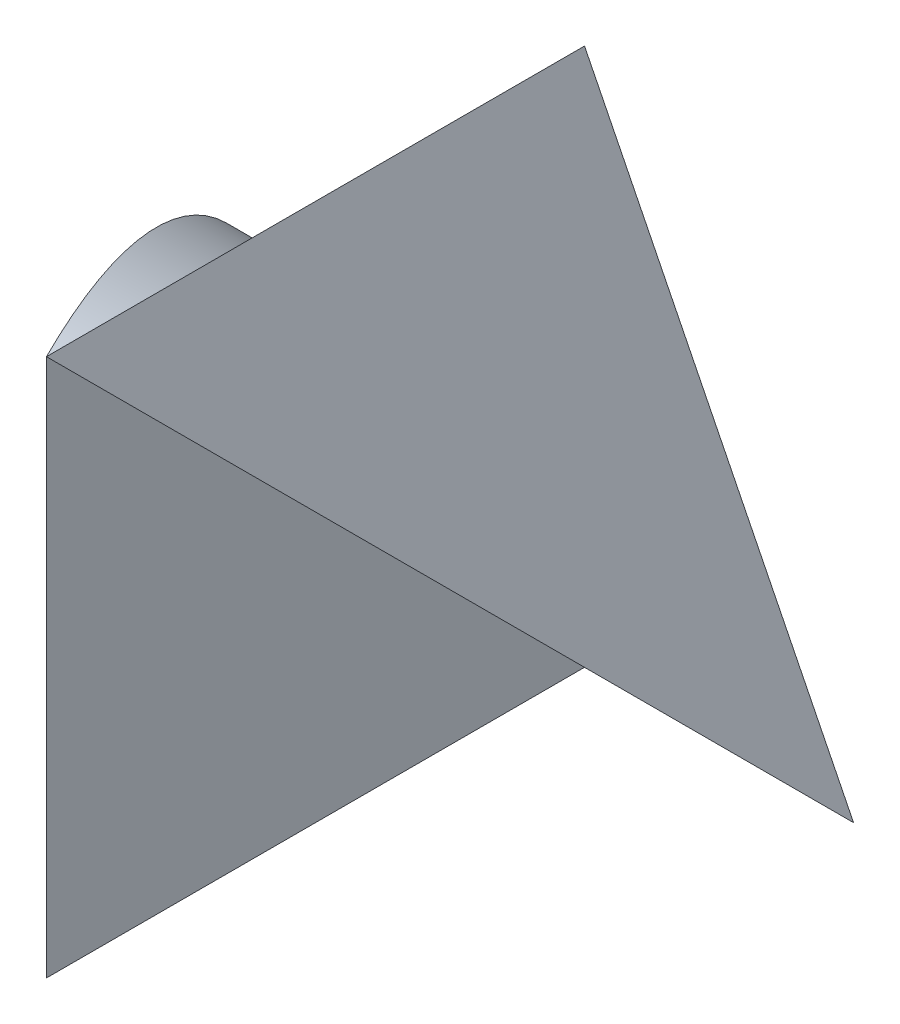
SolidWorks part; units mm, degrees
ref_plane "Front" through (0, 0, 0) normal (0, 0, 1) x (1, 0, 0)
ref_plane "Top" through (0, 0, 0) normal (0, 1, 0) x (1, 0, 0)
ref_plane "Right" through (0, 0, 0) normal (1, 0, 0) x (0, 0, -1)
sketch "Sketch1" plane through (0, 0, 0) normal (0, 1, 0) x (1, 0, 0)
  line L1 (-2, -2) -> (2, -2)
  line L2 (-2, -2) -> (-2, 2)
  line L3 (-2, 2) -> (2, 2)
  line L4 (2, -2) -> (2, 2)
  line L5 (-2, -2) -> (2, 2) construction
  line L6 (-2, 2) -> (2, -2) construction
  point P0 (0, 0)
  dimension "D1" = 4
  dimension "D2" = 4
extrude "Boss-Extrude1" add sketch "Sketch1" along normal blind 4
sketch3d "3DSketch1"
  line L0 (0, 4, 2) -> (-2, 4, -2)
  line L1 (-2, 4, 2) -> (2, 4, 2) construction
  line L2 (-2, 4, -2) -> (-2, 0, -2)
ref_plane "Plane1" through (-0.8, 0, 0.4) normal (-0.8944, 0, 0.4472) x (0.4472, 0, 0.8944)
sketch "Sketch3" plane through (-0.8, 0, 0.4) normal (-0.8944, 0, 0.4472) x (0.4472, 0, 0.8944)
  arc A0 (-2.6833, 0) -> (1.7889, 4) centre (1.8041, -0.5171) cw
sketch3d "3DSketch2"
  line L0 (-2, 0, -2) -> (0, 0, 2)
  line L1 (-2, 0, 2) -> (2, 0, 2) construction
  line L2 (0, 0, 2) -> (0, 4, 2)
  arc A0 (-2, 0, -2) -> (0, 4, 2) centre (0.0068, -0.5171, 2.0137) cw
  point P8 (4.0471, -0.5171, -0.0064)
extrude "Cut-Extrude1" cut sketch "3DSketch2" along direction (1, 0, 0) on the side against the normal blind 10
sketch "Sketch4" plane through (-2, 0, 0) normal (-1, 0, 0) x (0, 0, 1)
  line L2 (2, 4) -> (-2, 4)
  line L3 (-2, 4) -> (-2, 0)
  line L4 (2, 4) -> (-2, 4)
  line L5 (-2, 4) -> (-2, 0)
  spline S1 degree 3 poles (-2, 0) (-1.7538, 2.3888) (-0.1507, 3.9919) (2, 4) knots 0 0 0 0 1 1 1 1 weights 1 0.831739 0.831739 1
  spline S2 degree 3 poles (-2, 0) (-1.7538, 2.3888) (-0.1507, 3.9919) (2, 4) knots 0 0 0 0 1 1 1 1 weights 1 0.831739 0.831739 1
  dimension "D1" = 0
extrude "Cut-Extrude2" cut sketch "Sketch4" against normal blind 2
fillet "Chamfer1" radius 4 1 edges at (2, 4, 0) profile chamfer first distance on face at (2, 2, 0)
sketch "Sketch5" plane through (0, 0, 0) normal (0, -1, 0) x (1, 0, 0)
  line L0 (0, 2) -> (2, -2)
  line L5 (2, 2) -> (0, 2)
  line L6 (2, -2) -> (2, 2)
  line L7 (0, -2) -> (2, -2)
  line L8 (0, 2) -> (0, -2)
  line L9 (2, 2) -> (0, 2)
  line L10 (2, -2) -> (2, 2)
  line L11 (0, -2) -> (2, -2)
  line L12 (0, 2) -> (0, -2)
  line M9 (2, -2) -> (2, 2)
  line M10 (2, 2) -> (0, 2)
  dimension "D1" = 0
extrude "Cut-Extrude3" cut sketch "Sketch5" against normal blind 12 contours L0 M10 M9 region at (1.3333, 0, 0.6667)
sketch "Sketch6" plane through (0, 0, 0) normal (1, 0, 0) x (0, 0, -1)
  line L3 (2, 0) -> (-2, 4)
  line L4 (-2, 4) -> (-2, 0)
  line L5 (-2, 0) -> (2, 0)
  line L6 (2, 0) -> (-2, 4)
  line L7 (-2, 4) -> (-2, 0)
  line L8 (-2, 0) -> (2, 0)
  dimension "D1" = 0
extrude "Cut-Extrude4" cut sketch "Sketch6" along normal blind 10
